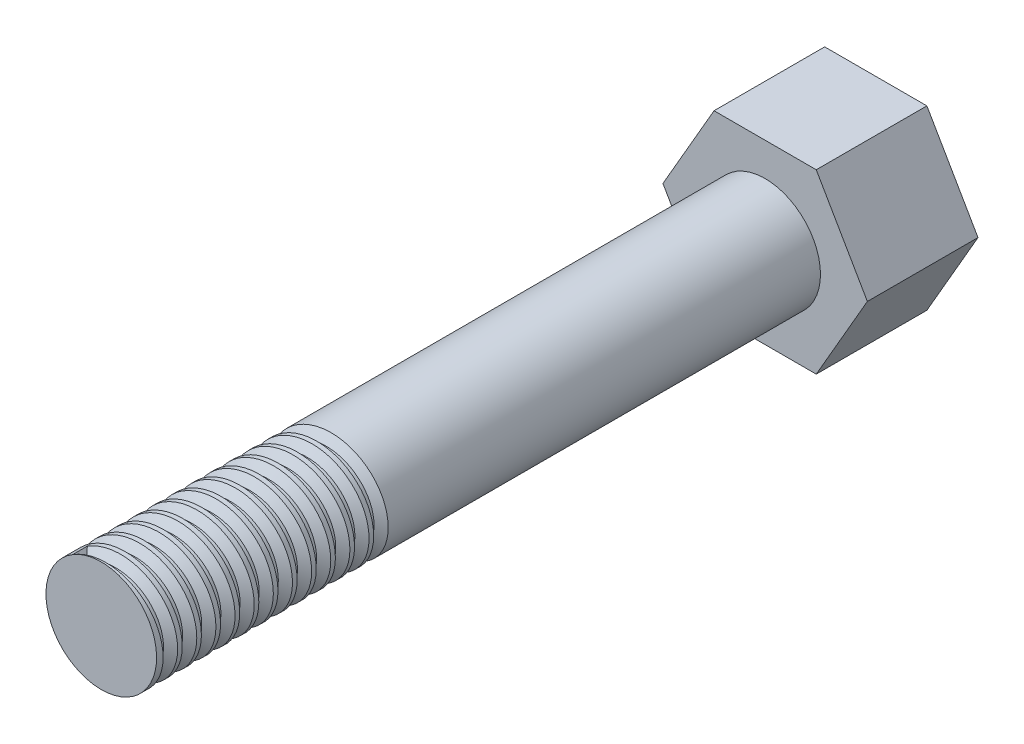
SolidWorks part; units mm, degrees
ref_plane "Front Plane" through (0, 0, 0) normal (0, 0, 1) x (1, 0, 0)
ref_plane "Top Plane" through (0, 0, 0) normal (0, 1, 0) x (1, 0, 0)
ref_plane "Right Plane" through (0, 0, 0) normal (1, 0, 0) x (0, 0, -1)
sketch "Sketch1" plane through (0, 0, 0) normal (0, 0, 1) x (1, 0, 0)
  line L14 (2.4632, 2.0551) -> (11.7008, 2.0551)
  line L15 (2.4632, -13.9449) -> (11.7008, -13.9449)
  line L16 (2.4632, 2.0551) -> (-2.1556, -5.9449)
  line L17 (-2.1556, -5.9449) -> (2.4632, -13.9449)
  line L18 (11.7008, 2.0551) -> (16.3196, -5.9449)
  line L19 (16.3196, -5.9449) -> (11.7008, -13.9449)
  circle A7 centre (7.082, -5.9449) radius 8
  dimension "D1" = 120
  dimension "D3" = 16
  dimension "D2" = 16
extrude "Boss-Extrude1" add sketch "Sketch1" along normal mid plane 10 contours A7 L14 L16 | A7 L16 L17 | A7 L17 L15 | A7 L15 L19 | A7 L19 L18 | A7 L18 L14 | A7 L14 region at (2.9477, 1.2158, 0) region at (11.2162, 1.2158, 0) region at (7.082, -5.9449, 0) region at (-1.1865, -5.9449, 0) region at (15.3505, -5.9449, 0) region at (2.9477, -13.1056, 0) region at (11.2162, -13.1056, 0)
sketch "Sketch2" plane through (0, 0, 5) normal (0, 0, 1) x (1, 0, 0)
  line L6 (11.7008, 2.0551) -> (2.4632, 2.0551)
  line L7 (16.3196, -5.9449) -> (11.7008, 2.0551)
  line L8 (11.7008, -13.9449) -> (16.3196, -5.9449)
  line L9 (2.4632, -13.9449) -> (11.7008, -13.9449)
  line L10 (-2.1556, -5.9449) -> (2.4632, -13.9449)
  line L11 (2.4632, 2.0551) -> (-2.1556, -5.9449)
  line L12 (11.7008, 2.0551) -> (2.4632, 2.0551)
  line L13 (16.3196, -5.9449) -> (11.7008, 2.0551)
  line L14 (11.7008, -13.9449) -> (16.3196, -5.9449)
  line L15 (2.4632, -13.9449) -> (11.7008, -13.9449)
  line L16 (-2.1556, -5.9449) -> (2.4632, -13.9449)
  line L17 (2.4632, 2.0551) -> (-2.1556, -5.9449)
  circle A0 centre (7.082, -5.9449) radius 5
  circle A1 centre (7.082, -5.9449) radius 8
  circle A2 centre (7.082, -5.9449) radius 8
  dimension "D1" = 0
  dimension "D2" = 0
extrude "Boss-Extrude2" add sketch "Sketch2" along normal blind 60 contours A0 region at (7.082, -5.9449, 5)
thread "Thread1" pitch 1.5 method cut profile "Thread Profile1" start angle 59, offset 0, length 20, pitch 1.73, diameter 10
ref_plane "Plane1" through (4.5068, -1.6591, 65) normal (-0.8572, -0.515, 0) x (-0.515, 0.8572, 0)
sketch "Thread Profile1" plane through (4.5068, -1.6591, 65) normal (-0.8572, -0.515, 0) x (-0.515, 0.8572, 0)
  line L0 (0, 0) -> (0, 1.5) construction
  line L11 (0, 0) -> (0, 1.3125)
  line L12 (0, 1.3125) -> (-0.8119, 0.8437)
  line L13 (-0.8119, 0.8437) -> (-0.8119, 0.4687)
  line L15 (-0.8119, 0.4687) -> (0, 0)
  line L17 (-0.8119, 0.6562) -> (0, 0.6562) construction
  point P2 (0, 0)
  dimension "Pitch" = 1.5
  dimension "Profile_Angle" = 60
  dimension "Profile_Land" = 0.375
  dimension "Profile_Height" = 0.8119
